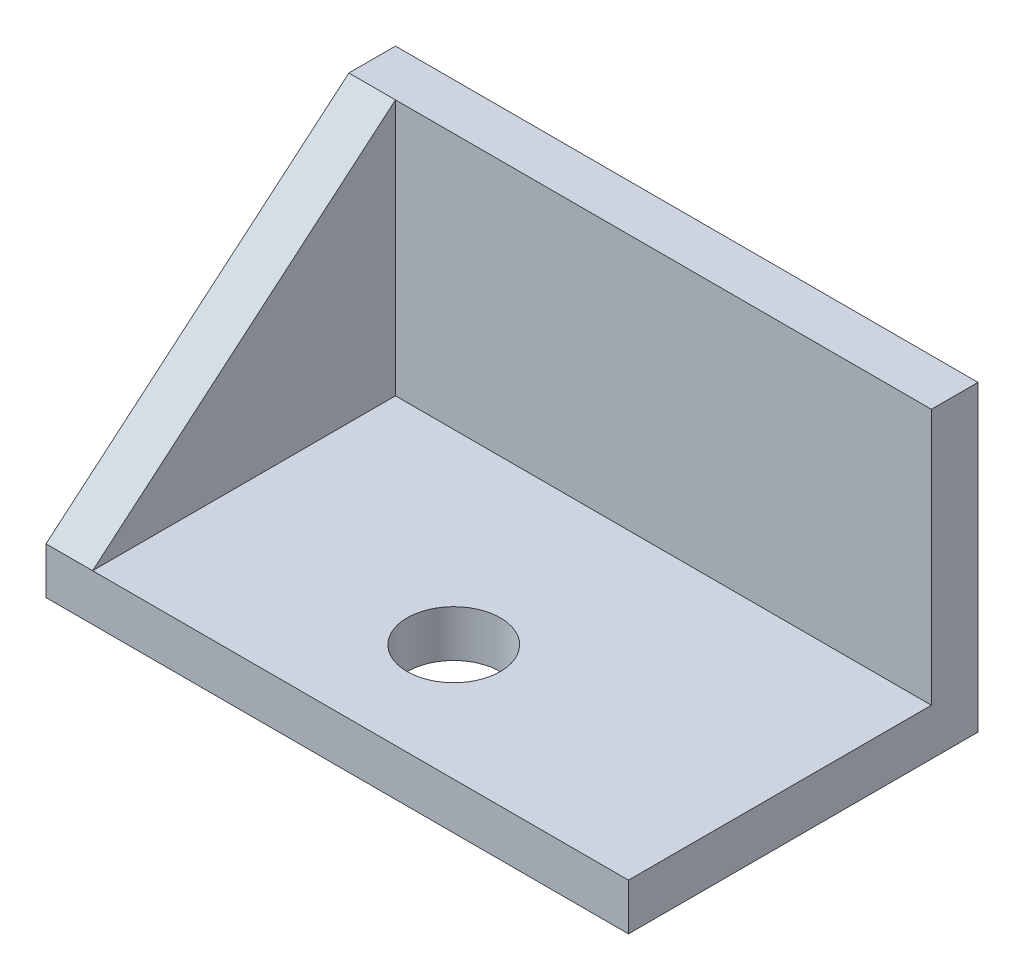
SolidWorks part; units mm, degrees
ref_plane "Front Plane" through (0, 0, 0) normal (0, 0, 1) x (1, 0, 0)
ref_plane "Top Plane" through (0, 0, 0) normal (0, 1, 0) x (1, 0, 0)
ref_plane "Right Plane" through (0, 0, 0) normal (1, 0, 0) x (0, 0, -1)
sketch "Sketch1" plane through (0, 0, 0) normal (1, 0, 0) x (0, 0, -1)
  line L0 (0, 0) -> (0, 65)
  line L1 (0, 65) -> (-10, 65)
  line L2 (-10, 65) -> (-10, 10)
  line L3 (-10, 10) -> (-75, 10)
  line L4 (-75, 10) -> (-75, 0)
  line L5 (-75, 0) -> (0, 0)
  line L6 (-10, 65) -> (-75, 10)
extrude "Boss-Extrude2" add sketch "Sketch1" along normal blind 125 contours L4 L5 L0 L1 L2 L3 region at (0, 0.9925, 37.5)
extrude "Boss-Extrude3" add sketch "Sketch1<3>" along normal blind 10 contours L2 L6 L3 region at (0, 28.3333, 31.6667)
sketch "Sketch1<3>" plane through (0, 0, 0) normal (1, 0, 0) x (0, 0, -1) same geometry as "Sketch1"
sketch "Sketch2" plane through (0, 10, 0) normal (0, 1, 0) x (1, 0, 0)
  line L0 (125, -75) -> (10, -75) construction
  line L2 (125, -10) -> (125, -75) construction
  circle A0 centre (62.5, -50) radius 10
  dimension "D1" = 25
  dimension "D2" = 62.5
extrude "Cut-Extrude1" cut sketch "Sketch2" against normal blind 10
